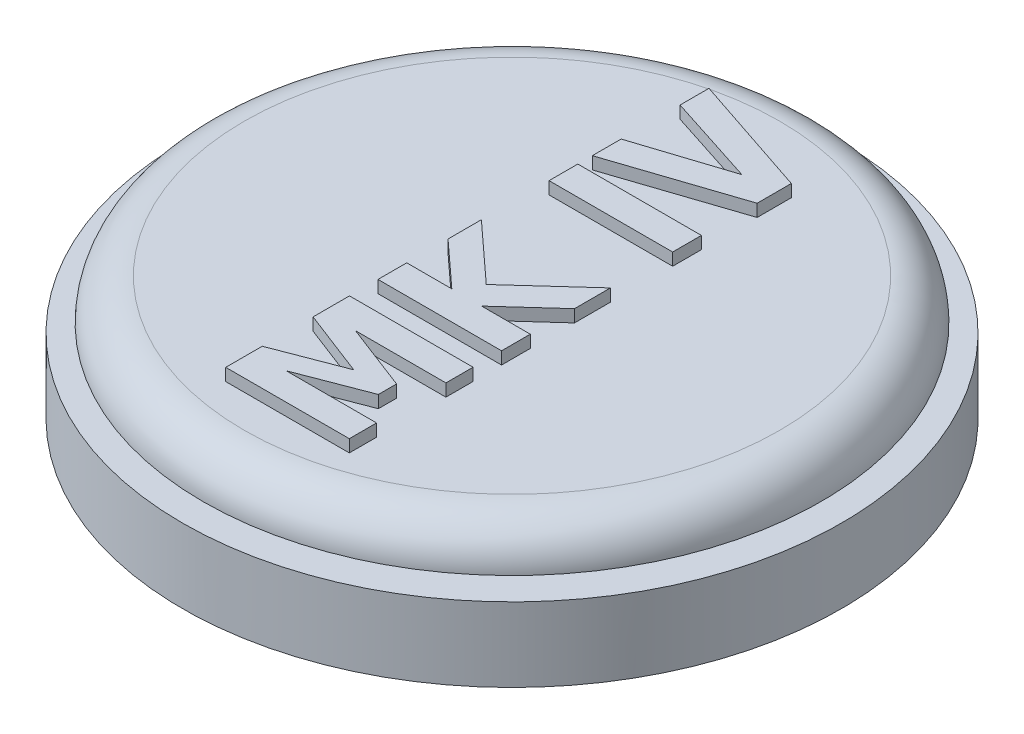
SolidWorks part; units mm, degrees
ref_plane "Спереди" through (0, 0, 0) normal (0, 0, 1) x (1, 0, 0)
ref_plane "Сверху" through (0, 0, 0) normal (0, 1, 0) x (1, 0, 0)
ref_plane "Справа" through (0, 0, 0) normal (1, 0, 0) x (0, 0, -1)
sketch "Sketch1" plane through (0, 0, 0) normal (0, 1, 0) x (1, 0, 0)
  circle A0 centre (0, 0) radius 12.3
  dimension "D1" = 24.6
extrude "Boss-Extrude1" add sketch "Sketch1" along normal blind 4
sketch "Sketch2" plane through (0, 4, 0) normal (0, 1, 0) x (1, 0, 0)
  circle A0 centre (0, 0) radius 15
  dimension "D1" = 30
extrude "Boss-Extrude2" add sketch "Sketch2" along normal blind 2
chamfer "Chamfer1" distance 0.5 angle 70 1 edges at (0, 0, 12.3) first distance on face at (0, 0, 12.3)
sketch "Sketch3" plane through (0, 6, 0) normal (0, 1, 0) x (1, 0, 0)
  line L0 (3.5, -14.586) -> (3.5, 14.586) construction
  line L1 (0, -15) -> (0, 15) construction
  circle A0 centre (0, 0) radius 15 construction
  text T0 "MK IV" font "DejaVu Sans Condensed" height 6
  dimension "D1" = 3.5
extrude "Boss-Extrude3" add sketch "Sketch3" along normal blind 0.6
sketch "Sketch4" plane through (0, 0, 0) normal (0, -1, 0) x (1, 0, 0)
  circle A0 centre (0, 0) radius 12.8
  circle A1 centre (0, 0) radius 16
  circle A2 centre (0, 0) radius 11.8 construction
  circle A3 centre (0, 0) radius 15 construction
  dimension "D1" = 1
  dimension "D2" = 1
extrude "Boss-Extrude4" add sketch "Sketch4" against normal offset from surface (3.6 mm away) 0.4 separate body up to face at (0, 4, 12.3)
fillet "Fillet1" radius 2 1 edges at (0, 6, 15)
